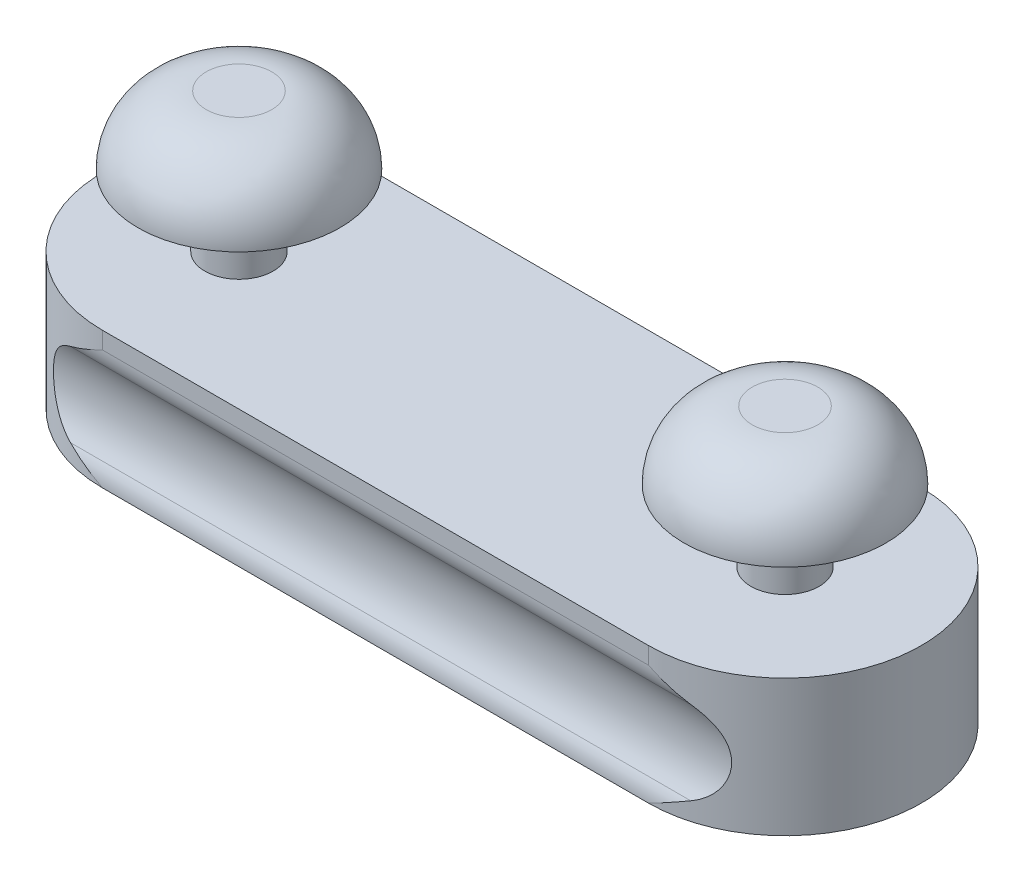
SolidWorks part; units mm, degrees
ref_plane "Front Plane" through (0, 0, 0) normal (0, 0, 1) x (1, 0, 0)
ref_plane "Top Plane" through (0, 0, 0) normal (0, 1, 0) x (1, 0, 0)
ref_plane "Right Plane" through (0, 0, 0) normal (1, 0, 0) x (0, 0, -1)
sketch "Sketch1" plane through (0, 0, 0) normal (0, 1, 0) x (1, 0, 0)
  line L0 (-12.7, 0) -> (12.7, 0) construction
  line L1 (-12.7, 6.35) -> (12.7, 6.35)
  line L3 (-12.7, -6.35) -> (12.7, -6.35)
  line L5 (-12.7, 6.35) -> (12.7, -6.35) construction
  line L6 (-12.7, -6.35) -> (12.7, 6.35) construction
  circle A0 centre (-12.7, 0) radius 1.5875
  circle A1 centre (12.7, 0) radius 1.5875
  arc A2 (-12.7, 6.35) -> (-12.7, -6.35) centre (-12.7, 0) ccw
  arc A3 (12.7, -6.35) -> (12.7, 6.35) centre (12.7, 0) ccw
  point P0 (0, 0)
  point P11 (0, 6.35)
  point P13 (0, 0)
  point P14 (-19.05, 0)
  point P15 (19.05, 0)
  dimension "D4" = 3.175
  dimension "D1" = 25.4
  dimension "D2" = 12.7
  dimension "D3" = 38.1
extrude "Boss-Extrude1" add sketch "Sketch1" along normal blind 6.35 contours L3 A3 L1 A2 A0 A1 | A0 | A1 region at (0, 0, 0) region at (-12.7, 0, 0) region at (12.7, 0, 0)
extrude "Boss-Extrude2" add sketch "Sketch1<4>" along normal blind 3.302 from surface contours A0 | A1 region at (-12.7, 0, 0) region at (12.7, 0, 0) starting at face at (0, 6.35, 0)
sketch "Sketch1<4>" plane through (0, 0, 0) normal (0, 1, 0) x (1, 0, 0) same geometry as "Sketch1"
sketch "Sketch2" plane through (0, 9.652, 0) normal (0, 1, 0) x (1, 0, 0)
  circle A0 centre (-12.7, 0) radius 4.699
  circle A1 centre (12.7, 0) radius 4.699
  dimension "D1" = 9.398
extrude "Boss-Extrude3" add sketch "Sketch2" along normal blind 3.175
sketch "Sketch3" plane through (0, 0, 0) normal (1, 0, 0) x (0, 0, -1)
  line L0 (-6.35, 0) -> (6.35, 0) construction
  line L2 (6.35, 6.35) -> (6.35, 5.5563)
  line L3 (6.35, 6.35) -> (6.35, 0) construction
  line L4 (6.35, 6.35) -> (6.35, 0)
  line L5 (0, 7.0548) -> (0, -7.0548) construction
  line L6 (-6.35, 6.35) -> (-6.35, 5.5563)
  line L7 (-6.35, 6.35) -> (-6.35, 0)
  arc A0 (6.35, 5.5563) -> (6.1104, 4.7176) centre (4.7625, 5.5562) cw
  arc A1 (6.1104, 4.7176) -> (5.5563, 2.7781) centre (9.2273, 2.7781) ccw
  arc A2 (5.5563, 2.7781) -> (6.1104, 0.8387) centre (9.2273, 2.7781) ccw
  arc A3 (6.1104, 0.8387) -> (6.35, 0) centre (4.7625, 0) cw
  arc A4 (-6.1104, 0.8387) -> (-6.35, 0) centre (-4.7625, 0) ccw
  arc A5 (-5.5563, 2.7781) -> (-6.1104, 0.8387) centre (-9.2273, 2.7781) cw
  arc A6 (-6.35, 5.5563) -> (-6.1104, 4.7176) centre (-4.7625, 5.5562) ccw
  arc A7 (-6.1104, 4.7176) -> (-5.5563, 2.7781) centre (-9.2273, 2.7781) cw
  dimension "D3" = 1.5875
  dimension "D1" = 0.7937
  dimension "D2" = 0.7937
extrude "Cut-Extrude1" cut sketch "Sketch3" against normal mid plane 40.64 contours A2 A3 L4 A0 A1 | A7 A6 L7 A4 A5 region at (0, 2.7781, -6.0342) region at (0, 2.7781, 6.0342)
fillet "Fillet1" radius 3.175 2 edges at (12.7, 12.827, 4.699) (-12.7, 12.827, 4.699)
equation "\"WallThickness\"=0.125"
equation "\"D1@Boss-Extrude2\"=\"WallThickness\"+.005"
